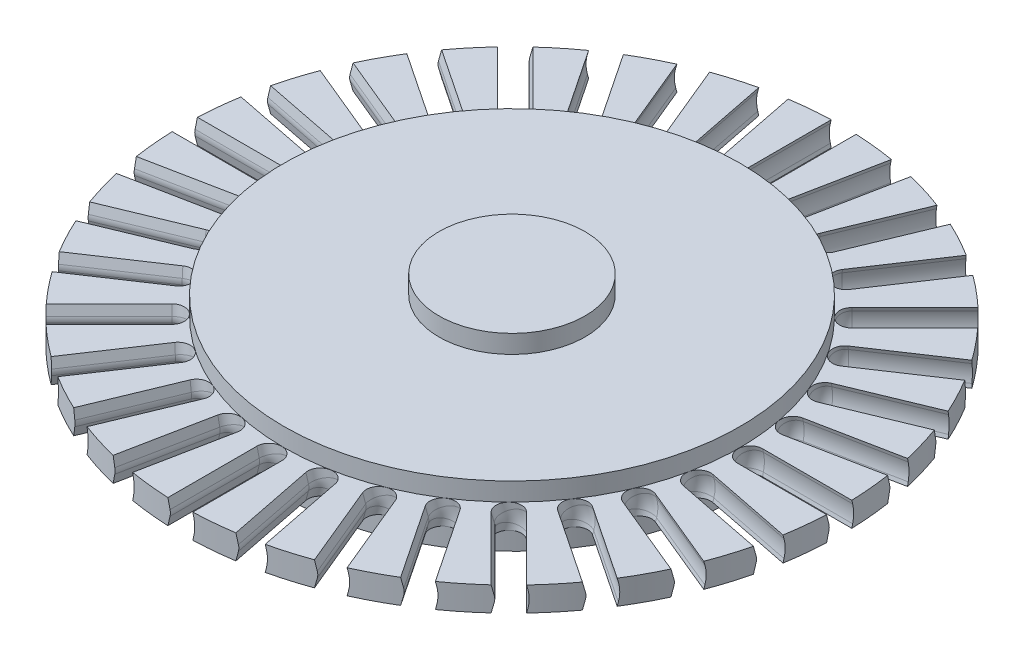
SolidWorks part; units mm, degrees
material "AISI 316 Annealed Stainless Steel Bar (SS)"
ref_plane "Front Plane" through (0, 0, 0) normal (0, 0, 1) x (1, 0, 0)
ref_plane "Top Plane" through (0, 0, 0) normal (0, 1, 0) x (1, 0, 0)
ref_plane "Right Plane" through (0, 0, 0) normal (1, 0, 0) x (0, 0, -1)
ref_axis "Axis1" through (0, 13.97, 0) along (0, -1, 0)
sketch "Sketch4" plane through (0, 0, 0) normal (0, 0, 1) x (1, 0, 0)
  line L1 (85.9536, -3.175) -> (85.9536, 3.175)
  line L2 (85.9536, 3.175) -> (59.4614, 3.175)
  line L4 (0, -12.7) -> (0, 12.7)
  line L6 (0, 0) -> (0, 12.7) construction
  line L9 (59.4614, -3.175) -> (85.9536, -3.175)
  line L12 (19.05, -12.7) -> (19.05, 12.7)
  line L16 (59.4614, 3.175) -> (59.4614, -3.175)
  line L18 (19.05, -12.7) -> (0, -12.7)
  line L20 (0, 12.7) -> (19.05, 12.7)
  line L22 (0, 0) -> (85.9536, 0) construction
  line L23 (19.05, 7.9375) -> (59.4614, 7.9375)
  line L24 (59.4614, 7.9375) -> (59.4614, 3.175)
  line L25 (19.05, -7.9375) -> (59.4614, -7.9375)
  line L26 (59.4614, -7.9375) -> (59.4614, -3.175)
  point P6 (0, 0)
  point P11 (85.9536, 0)
  dimension "D1" = 171.9072
  dimension "D3" = 6.35
  dimension "D4" = 118.9228
  dimension "D8" = 38.1
  dimension "D5" = 25.4
  dimension "D6" = 15.875
revolve "Disc" add sketch "Sketch4" angle 360 about L6
ref_plane "Plane1" through (85.9536, 0, 0) normal (1, 0, 0) x (0, 0, -1)
sketch "Endmill" plane through (0, 0, 0) normal (0, 1, 0) x (1, 0, 0)
  line L0 (110.2614, 3.175) -> (62.6364, 3.175)
  line L1 (62.6364, -3.175) -> (110.2614, -3.175)
  line L2 (110.2614, -3.175) -> (110.2614, 3.175)
  line L3 (0, 0) -> (59.4614, 0) construction
  arc A0 (62.6364, 3.175) -> (62.6364, -3.175) centre (62.6364, 0) ccw
  dimension "D1" = 6.35
  dimension "D2" = 59.4614
  dimension "D3" = 50.8
sketch "Sketch9" plane through (85.9536, 0, 0) normal (1, 0, 0) x (0, 0, -1)
  line L0 (-2.8893, 12.7) -> (-0.178, 1.4932)
  line L1 (-0.178, -1.4932) -> (-2.8893, -12.7)
  line L2 (0, 12.7) -> (0, -12.7) construction
  arc A0 (-0.178, 1.4932) -> (-0.178, -1.4932) centre (-6.35, 0) cw
  point P4 (0, 0)
  point P10 (0, 0)
  dimension "D2" = 6.35
  dimension "D1" = 13.6
  dimension "D3" = 25.4
sweep "Blade Cutout" cut profiles "Endmill" path "Sketch9"
pattern_circular "Blades" count 32 over 360 about axis through (0, 13.97, 0) along (0, -1, 0) of "Blade Cutout"
sketch "Sketch7" plane through (0, 0, 0) normal (0, 1, 0) x (1, 0, 0)
  line L0 (38.1, 0) -> (63.5, 0) construction
  line L1 (38.1, 3.175) -> (63.5, 3.175)
  line L2 (38.1, -3.175) -> (63.5, -3.175)
  arc A0 (38.1, 3.175) -> (38.1, -3.175) centre (38.1, 0) ccw
  arc A1 (63.5, -3.175) -> (63.5, 3.175) centre (63.5, 0) ccw
  point P3 (50.8, 0)
  dimension "D1" = 3.175
  dimension "D2" = 63.5
  dimension "D3" = 25.4
extrude "Mass Cutout" [suppressed] cut sketch "Sketch7" against normal through all both and the other way through all
pattern_circular "Cutouts" [suppressed] count 16 over 360 about axis through (0, 13.97, 0) along (0, -1, 0) of bodies 117
equation "\"D1@Sketch4\"=2*\"rotor tip@[TP] [Turb] Turbine.Assembly\""
equation "\"D4@Sketch4\"=2*\"rotor base@[TP] [Turb] Turbine.Assembly\""
equation "\"D2@Endmill\"=\"rotor base@[TP] [Turb] Turbine.Assembly\""
equation "\"D1@Sketch9\"=\"blade angle@[TP] [Turb] Turbine.Assembly\""
